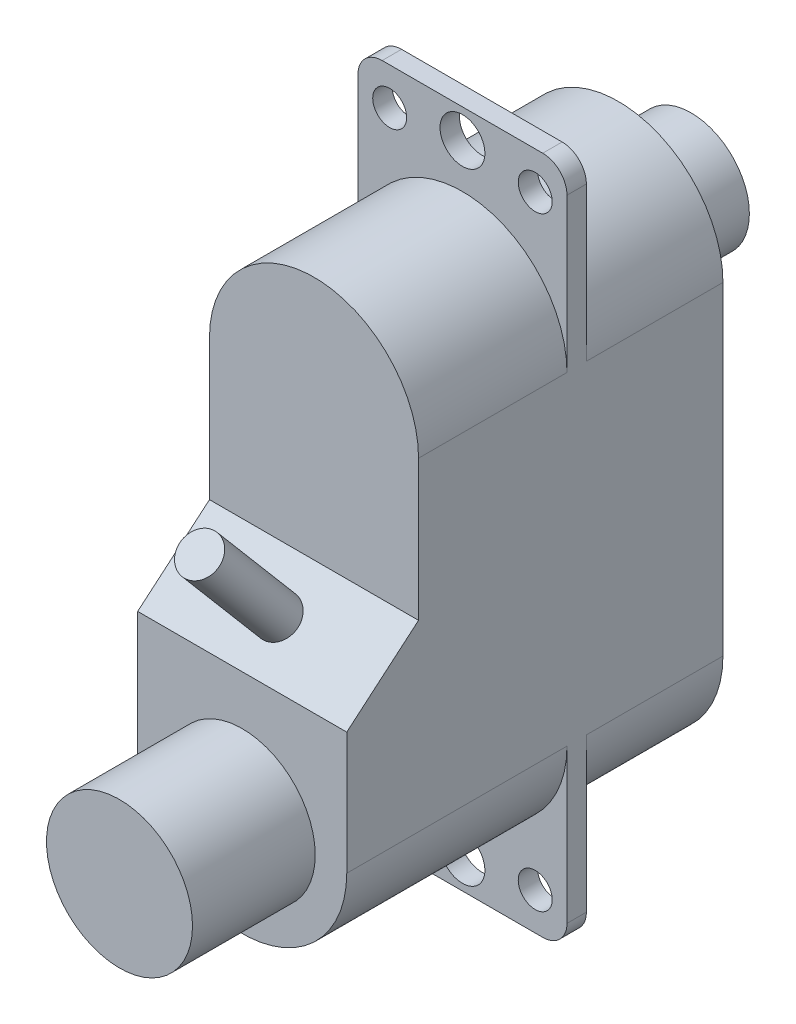
SolidWorks part; units mm, degrees
ref_plane "Front Plane" through (0, 0, 0) normal (0, 0, 1) x (1, 0, 0)
ref_plane "Top Plane" through (0, 0, 0) normal (0, 1, 0) x (1, 0, 0)
ref_plane "Right Plane" through (0, 0, 0) normal (1, 0, 0) x (0, 0, -1)
sketch "Sketch1" plane through (0, 0, 0) normal (0, 0, 1) x (1, 0, 0)
  circle A0 centre (0, 0) radius 2.4
  dimension "D1" = 4.8
extrude "Boss-Extrude1" add sketch "Sketch1" along normal blind 3
sketch "Sketch2" plane through (0, 0, 3) normal (0, 0, 1) x (1, 0, 0)
  line L0 (0, 0) -> (0, -13.34) construction
  line L1 (4.31, 0) -> (4.31, -13.34)
  line L2 (-4.31, 0) -> (-4.31, -13.34)
  line L3 (0, 4.31) -> (12.7239, 4.31) construction
  line L5 (0, -17.65) -> (15.2884, -17.65) construction
  arc A0 (4.31, 0) -> (-4.31, 0) centre (0, 0) ccw
  arc A1 (-4.31, -13.34) -> (4.31, -13.34) centre (0, -13.34) ccw
  point P3 (0, -6.67)
  dimension "D1" = 8.62
  dimension "D2" = 21.96
extrude "Boss-Extrude2" add sketch "Sketch2" along normal blind 15.51
sketch "Sketch3" plane through (0, 0, 0) normal (1, 0, 0) x (0, 0, -1)
  line L0 (-18.51, 4.31) -> (-15.55, 4.31)
  line L1 (-15.55, 4.31) -> (-15.55, -5.79)
  line L2 (-15.55, -5.79) -> (-18.51, -8.3)
  line L3 (-18.51, -13.34) -> (-18.51, 0) construction
  line L4 (-18.51, -8.3) -> (-18.51, 4.31)
  line L5 (-3, 0) -> (-3, 4.31) construction
  dimension "D1" = 12.55
  dimension "D2" = 9.35
  dimension "D3" = 10.1
extrude "Cut-Extrude1" cut sketch "Sketch3" against normal through all both and the other way through all
sketch "Sketch4" plane through (0, 0, 18.51) normal (0, 0, 1) x (1, 0, 0)
  circle A0 centre (0, -13.34) radius 3.01
  dimension "D1" = 6.02
extrude "Boss-Extrude3" add sketch "Sketch4" along normal blind 5.06
ref_plane "Plane1" through (0, 0, 8.63) normal (0, 0, -1) x (-1, 0, 0)
sketch "Sketch5" plane through (0, 0, 8.63) normal (0, 0, -1) x (-1, 0, 0)
  line L1 (-3.31, 7.33) -> (3.31, 7.33)
  line L2 (-4.31, 6.33) -> (-4.31, -19.67)
  line L3 (-3.31, -20.67) -> (3.31, -20.67)
  line L4 (4.31, 6.33) -> (4.31, -19.67)
  line L5 (4.31, 0) -> (4.31, -13.34) construction
  line L6 (0, 0) -> (0, 7.33) construction
  line L8 (4.31, -6.67) -> (10.5668, -6.67) construction
  arc A0 (-4.31, -19.67) -> (-3.31, -20.67) centre (-3.31, -19.67) ccw
  arc A1 (3.31, 7.33) -> (4.31, 6.33) centre (3.31, 6.33) cw
  arc A2 (-3.31, 7.33) -> (-4.31, 6.33) centre (-3.31, 6.33) ccw
  arc A3 (3.31, -20.67) -> (4.31, -19.67) centre (3.31, -19.67) ccw
  circle A4 centre (0, 6.13) radius 0.925
  circle A5 centre (3, 5.7908) radius 0.7
  circle A6 centre (-3, 5.7908) radius 0.7
  circle A7 centre (3, -19.1308) radius 0.7
  circle A8 centre (0, -19.47) radius 0.925
  circle A9 centre (-3, -19.1308) radius 0.7
  point P4 (0, 7.33)
  point P14 (4.31, -6.67)
  point P17 (4.31, -6.67)
  dimension "D1" = 1
  dimension "D2" = 1
  dimension "D4" = 1.85
  dimension "D5" = 1.4
  dimension "D7" = 25.6
  dimension "D3" = 28
  dimension "D6" = 6
extrude "Boss-Extrude4" add sketch "Sketch5" against normal blind 0.8
sketch "Sketch6" plane through (0, 4.3023, 3.6483) normal (0, 0.7627, 0.6468) x (1, 0, 0)
  circle A0 centre (0, -17.5504) radius 0.8231
extrude "Boss-Extrude5" add sketch "Sketch6" along normal blind 5
ref_axis "Axis1" through (0, 0, 8.9133) along (0, 0, -1)
ref_plane "Plane2" through (-4.18, 0.7371, 0) normal (-0.9848, 0.1736, 0) x (0, 0, -1)
ref_plane "Plane3" through (0, 0, 0) normal (0.4226, 0.9063, 0) x (0, 0, -1)
